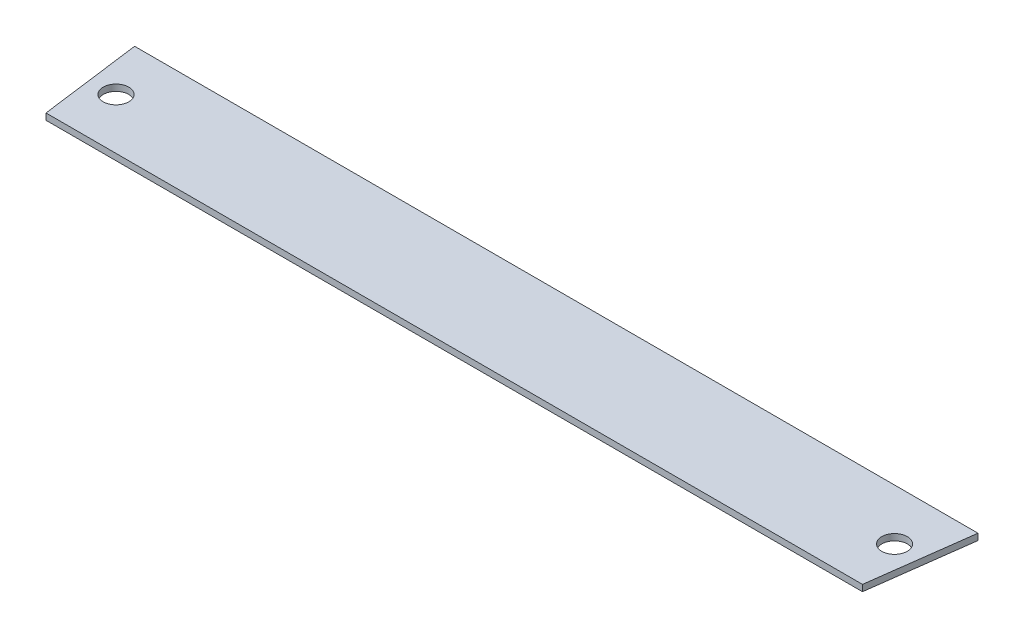
SolidWorks part; units mm, degrees
ref_plane "Front Plane" through (0, 0, 0) normal (0, 0, 1) x (1, 0, 0)
ref_plane "Top Plane" through (0, 0, 0) normal (0, 1, 0) x (1, 0, 0)
ref_plane "Right Plane" through (0, 0, 0) normal (1, 0, 0) x (0, 0, -1)
sketch "Sketch1" plane through (0, 0, 0) normal (0, 1, 0) x (1, 0, 0)
  line L0 (-203.2, 0) -> (203.2, 0) construction
  line L1 (203.2, -25.4) -> (-203.2, -25.4)
  line L2 (203.2, -25.4) -> (203.2, 25.4)
  line L3 (203.2, 25.4) -> (-203.2, 25.4)
  line L4 (-203.2, -25.4) -> (-203.2, 25.4)
  line L5 (203.2, -25.4) -> (-203.2, 25.4) construction
  line L6 (203.2, 25.4) -> (-203.2, -25.4) construction
  line L7 (-203.2, -25.4) -> (-209.8879, 25.4)
  line L8 (-209.8879, 25.4) -> (-203.2, 25.4)
  line L9 (203.2, -25.4) -> (209.8879, 25.4)
  line L10 (209.8879, 25.4) -> (203.2, 25.4)
  circle A0 centre (-193.75, 0) radius 6.35
  circle A1 centre (193.75, 0) radius 6.35
  point P0 (0, 0)
  dimension "D1" = 406.4
  dimension "D5" = 12.7
  dimension "D2" = 50.8
  dimension "D3" = 387.5
  dimension "D4" = 193.75
  dimension "D6" = 7.5
  dimension "D7" = 7.5
extrude "Boss-Extrude1" add sketch "Sketch1" along normal blind 3.175 contours L4 L1 L2 L3 A1 A0 | L8 L7 L4 | L9 L10 L2 region at (0, 0, 0) region at (205.4293, 0, -8.4667) region at (-205.4293, 0, -8.4667)
